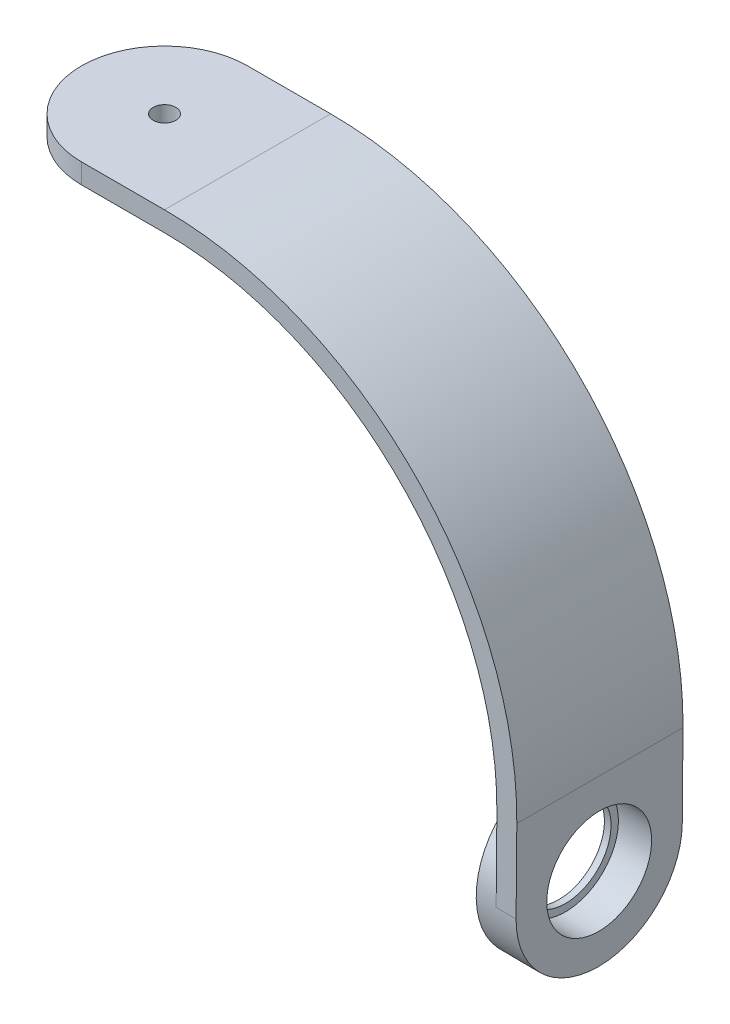
SolidWorks part; units mm, degrees
ref_plane "Front Plane" through (0, 0, 0) normal (0, 0, 1) x (1, 0, 0)
ref_plane "Top Plane" through (0, 0, 0) normal (0, 1, 0) x (1, 0, 0)
ref_plane "Right Plane" through (0, 0, 0) normal (1, 0, 0) x (0, 0, -1)
sketch "Sketch2" plane through (0, 0, 0) normal (0, 0, 1) x (1, 0, 0)
  line L0 (0, 0) -> (0, 50) construction
  line L1 (0, 0) -> (49.9981, -0.4363) construction
  line L4 (0, 53) -> (-25, 53)
  line L5 (-25, 53) -> (-25, 50)
  line L6 (-25, 50) -> (0, 50)
  line L7 (49.9981, -0.4363) -> (49.7799, -25.4354)
  line L8 (49.7799, -25.4354) -> (52.7798, -25.4616)
  line L9 (52.7798, -25.4616) -> (52.998, -0.4625)
  arc A0 (0, 50) -> (49.9981, -0.4363) centre (0, 0) cw
  arc A1 (0, 53) -> (52.998, -0.4625) centre (0, 0) cw
  dimension "D2" = 50
  dimension "D1" = 90.5
  dimension "D3" = 3
  dimension "D4" = 25
  dimension "D5" = 25
extrude "Boss-Extrude1" add sketch "Sketch2" along normal blind 25
sketch "Sketch6" plane through (52.998, -0.4625, 0) normal (1, -0.0087, 0) x (0, 0, -1)
  line L1 (-25, 0) -> (0, -25) construction
  line L4 (0, 0) -> (-25, -25) construction
  circle A1 centre (-12.5, -12.5) radius 7.89
  dimension "D1" = 15.78
extrude "Cut-Extrude1" cut sketch "Sketch6" against normal up to next
fillet "Fillet1" radius 12.5 2 edges at (51.2799, -25.4485, 0) (51.2799, -25.4485, 25)
fillet "Fillet2" radius 12.5 2 edges at (-25, 51.5, 25) (-25, 51.5, 0)
sketch "Sketch7" plane through (49.9981, -0.4363, 0) normal (-1, 0.0087, 0) x (0, 0, 1)
  circle A0 centre (12.5, -12.5) radius 12.5
  circle A1 centre (12.5, -12.5) radius 6.79
  dimension "D1" = 25
  dimension "D2" = 13.58
extrude "Boss-Extrude2" add sketch "Sketch7" along normal blind 3
sketch "Sketch8" plane through (52.998, -0.4625, 0) normal (1, -0.0087, 0) x (0, 0, -1)
  circle A0 centre (-12.5, -12.5) radius 7.89
  dimension "D1" = 15.78
extrude "Cut-Extrude2" cut sketch "Sketch8" against normal blind 5
sketch "Sketch9" plane through (0, 53, 0) normal (0, 1, 0) x (1, 0, 0)
  circle A0 centre (-12.5, -12.5) radius 1.7
  dimension "D1" = 3.4
extrude "Cut-Extrude3" cut sketch "Sketch9" against normal up to next
equation "\"D1@Sketch2\"=362/4"
